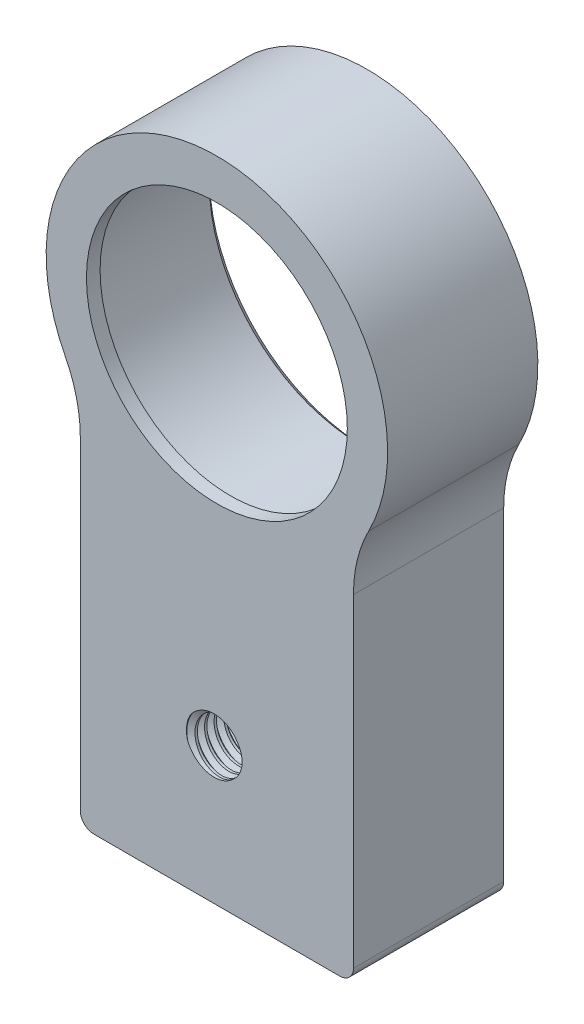
SolidWorks part; units mm, degrees
ref_plane "Plan de face" through (0, 0, 0) normal (0, 0, 1) x (1, 0, 0)
ref_plane "Plan de dessus" through (0, 0, 0) normal (0, 1, 0) x (1, 0, 0)
ref_plane "Plan de droite" through (0, 0, 0) normal (1, 0, 0) x (0, 0, -1)
sketch "Esquisse1" plane through (0, 0, 0) normal (0, 0, 1) x (1, 0, 0)
  line L0 (-10, 20) -> (-10, 27.5)
  line L2 (-10, 20) -> (-10, 0)
  line L3 (-10, 0) -> (10, 0)
  line L4 (10, 20) -> (10, 0)
  line L5 (10, 20) -> (10, 27.5)
  arc A0 (10, 27.5) -> (-10, 27.5) centre (0, 35) ccw
  circle A1 centre (0, 10) radius 1.85
  dimension "D3" = 25
  dimension "D4" = 3.7
  dimension "D1" = 20
  dimension "D2" = 20
  dimension "D5" = 10
  dimension "D6" = 35
extrude "Boss.-Extru.1" add sketch "Esquisse1" along normal blind 11
sketch "Esquisse2" plane through (0, 0, 0) normal (0, 0, -1) x (-1, 0, 0)
  circle A0 centre (0, 35) radius 11.05
  dimension "D1" = 22.1
extrude "Enlèv. mat.-Extru.1" cut sketch "Esquisse2" against normal blind 10
sketch "Esquisse3" plane through (0, 0, 10) normal (0, 0, -1) x (-1, 0, 0)
  circle A0 centre (0, 35) radius 9.55
  circle A1 centre (0, 35) radius 11.05 construction
  circle A2 centre (0, 35) radius 11.05 construction
  dimension "D1" = 1.5
extrude "Enlèv. mat.-Extru.2" cut sketch "Esquisse3" against normal through all
sketch "Esquisse4" plane through (0, 0, 0) normal (0, 0, -1) x (-1, 0, 0)
  line L0 (-7.75, 13) -> (-7.75, 0)
  line L1 (10, 0) -> (-10, 0) construction
  line L2 (-7.75, 0) -> (7.75, 0)
  line L3 (7.75, 0) -> (7.75, 13)
  arc A0 (7.75, 13) -> (-7.75, 13) centre (0, 13) ccw
  circle A1 centre (0, 35) radius 11.05 construction
  dimension "D1" = 15.5
  dimension "D2" = 22
extrude "Enlèv. mat.-Extru.3" cut sketch "Esquisse4" against normal blind 3
chamfer "Chanfrein1" distance 0.5 angle 45 4 edges at (-7.75, 0, 1.5) (7.75, 0, 1.5) (-1.85, 10, 3) (-11.05, 35, 0)
fillet "Congé1" radius 10 2 edges at (10, 27.5, 5.5) (-10, 27.5, 5.5)
fillet "Congé2" radius 1 2 edges at (-10, 0, 5.5) (10, 0, 5.5)
thread "Filetage1" pitch 0.7 method cut trim with start face yes trim with end face yes profile "Profil de filetage1" start angle 0, offset 1, length 0, pitch 0.7, diameter 3.7
ref_plane "Plan1" through (1.85, 10, 2) normal (0, -1, 0) x (1, 0, 0)
sketch "Profil de filetage1" plane through (1.85, 10, 2) normal (0, -1, 0) x (1, 0, 0)
  line L0 (0, 0) -> (0, 0.7) construction
  line L1 (0, 0) -> (0.3789, 0.2187)
  line L2 (0.3789, 0.2187) -> (0.3789, 0.3062)
  line L3 (0.3789, 0.3062) -> (0, 0.525)
  line L4 (0.3789, 0.2625) -> (0, 0.2625) construction
  line L11 (0, 0) -> (0, 0.525)
  point P2 (0, 0)
  dimension "Pitch" = 0.7
  dimension "Profile_Angle" = 60
  dimension "Profile_Land" = 0.0875
  dimension "Profile_Height" = 0.3789
